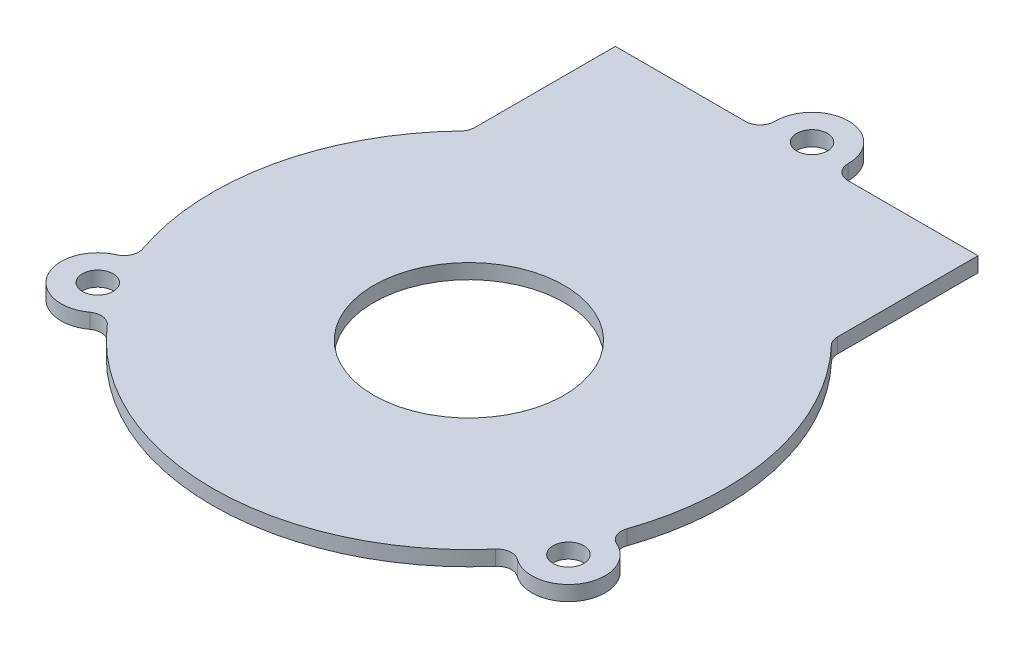
SolidWorks part; units mm, degrees
ref_plane "Front Plane" through (0, 0, 0) normal (0, 0, 1) x (1, 0, 0)
ref_plane "Top Plane" through (0, 0, 0) normal (0, 1, 0) x (1, 0, 0)
ref_plane "Right Plane" through (0, 0, 0) normal (1, 0, 0) x (0, 0, -1)
sketch "Sketch13" plane through (0, 0, 0) normal (0, 1, 0) x (1, 0, 0)
  circle A0 centre (0, 0) radius 35
extrude "Boss-Extrude3" add sketch "Sketch13" along normal blind 2.032
sketch "Sketch14" plane through (0, 2.032, 0) normal (0, 1, 0) x (1, 0, 0)
  line L0 (-24.7478, 24.7497) -> (24.7477, 24.7498)
  line L1 (-24.7478, 24.7497) -> (-24.7479, 44.7452)
  line L2 (24.7477, 24.7498) -> (24.7476, 44.7454)
  line L3 (-24.7479, 44.7452) -> (24.7476, 44.7454)
  line L4 (0, 0) -> (60.4611, -34.8658) construction
  line L5 (0, 0) -> (-56.6044, -32.6614) construction
  line L7 (-3.939, 44.1714) -> (-8.8985, 44.1714)
  line L8 (-3.939, 44.1714) -> (-3.939, 47.547)
  line L9 (-3.939, 47.547) -> (-8.8985, 47.547)
  line L10 (-8.8985, 44.1714) -> (-8.8985, 47.547)
  arc A0 (0, 35) -> (-24.7478, 24.7497) centre (0, 0) ccw construction
  circle A1 centre (0, 0) radius 35 construction
  arc A2 (0, 35) -> (-30.3109, -17.4999) centre (0, 0) ccw construction
  arc A3 (0, 35) -> (30.3118, -17.4984) centre (0, 0) ccw
  arc A4 (0, 35) -> (24.7477, 24.7498) centre (0, 0) ccw construction
  circle A5 centre (32.1365, -18.5413) radius 2.1017
  circle A6 centre (32.1365, -18.5413) radius 4.9951
  circle A7 centre (-32.1465, -18.5162) radius 2.0981
  circle A8 centre (-32.1465, -18.5162) radius 4.9995
extrude "Boss-Extrude4" add sketch "Sketch14" against normal up to surface (2.032 mm away) contours L0 L1 L3 L2 up to face at (0, 0, 35)
sketch "Sketch15" plane through (0, 2.032, 0) normal (0, 1, 0) x (1, 0, 0)
  line L0 (0, 0) -> (0, 62.3966) construction
  line L1 (-0.0001, 44.7453) -> (0, 46.8414) construction
  line L2 (-24.7479, 44.7452) -> (24.7476, 44.7454) construction
  circle A0 centre (0, 46.8414) radius 2.0961
  circle A1 centre (0, 46.8414) radius 4.996
extrude "Boss-Extrude11" add sketch "Sketch15" against normal up to surface (2.032 mm away) contours A1 | A0 up to face at (-0.0001, 0, -19.8101)
extrude "Boss-Extrude12" add sketch "Sketch14<6>" against normal up to surface (2.032 mm away) contours A6 up to face at (0, 0, -29.3038)
sketch "Sketch14<6>" plane through (0, 2.032, 0) normal (0, 1, 0) x (1, 0, 0) same geometry as "Sketch14"
extrude "Boss-Extrude14" add sketch "Sketch14<8>" against normal up to surface (2.032 mm away) contours L0 A5 region at (32.1365, 2.032, 18.5413) up to face at (5.9749, 0, -21.2696)
sketch "Sketch14<8>" plane through (0, 2.032, 0) normal (0, 1, 0) x (1, 0, 0) same geometry as "Sketch14"
hole_wizard "Ø4.2 (4.2) Diameter Hole1" positions "Sketch22" profile "Sketch23" hole size "Ø4.2" standard "ANSI Metric" end condition through all
sketch "Sketch22" plane through (0, 2.032, 0) normal (0, 1, 0) x (1, 0, 0)
  point P0 (32.1248, -18.5356)
sketch "Sketch23" plane through (32.1248, 2.032, 18.5356) normal (1, 0, 0) x (0, 0, 1)
  line L0 (0, 0) -> (0, 2.032)
  line L1 (0, 2.032) -> (2.1, 2.032)
  line L2 (2.1, 2.032) -> (2.1, 0)
  line L5 (2.1, 0) -> (0, 0)
  line L11 (0, -6.35) -> (0, 107.95) construction
  dimension "Thru Hole Dia." = 4.2
  dimension "Thru Hole Depth" = 2.032
extrude "Boss-Extrude15" add sketch "Sketch14<11>" against normal up to surface (2.032 mm away) contours A8 up to face at (32.1248, 0, 20.6356)
sketch "Sketch14<11>" plane through (0, 2.032, 0) normal (0, 1, 0) x (1, 0, 0) same geometry as "Sketch14"
hole_wizard "Ø4.2 (4.2) Diameter Hole2" positions "Sketch26" profile "Sketch27" hole size "Ø4.2" standard "ANSI Metric" end condition through all
sketch "Sketch26" plane through (0, 2.032, 0) normal (0, 1, 0) x (1, 0, 0)
  point P0 (-32.148, -18.5088)
  point P2 (-32.148, -18.5088)
sketch "Sketch27" plane through (-32.148, 2.032, 18.5088) normal (1, 0, 0) x (0, 0, 1)
  line L0 (0, 0) -> (0, 2.032)
  line L1 (0, 2.032) -> (2.1, 2.032)
  line L2 (2.1, 2.032) -> (2.1, 0)
  line L5 (2.1, 0) -> (0, 0)
  line L11 (0, -6.35) -> (0, 107.95) construction
  dimension "Thru Hole Dia." = 4.2
  dimension "Thru Hole Depth" = 2.032
fillet "Fillet4" radius 2 1 edges at (-24.7478, 1.016, -24.7497)
fillet "Fillet6" radius 2 1 edges at (-32.2839, 1.016, 13.5185)
fillet "Fillet7" radius 2 1 edges at (-27.8924, 1.016, 21.1427)
fillet "Fillet8" radius 2 1 edges at (27.8812, 1.016, 21.1574)
fillet "Fillet9" radius 2 1 edges at (32.2715, 1.016, 13.548)
fillet "Fillet10" radius 2 1 edges at (24.7477, 1.016, -24.7498)
fillet "Fillet11" radius 2 1 edges at (4.535, 1.016, -44.7453)
fillet "Fillet12" radius 2 1 edges at (-4.535, 1.016, -44.7453)
sketch "Sketch28" plane through (0, 2.032, 0) normal (0, 1, 0) x (1, 0, 0)
  circle A0 centre (0, 0) radius 5
extrude "Cut-Extrude1" cut sketch "Sketch28" against normal up to surface (2.032 mm away) up to face at (-32.148, 0, 20.6088)
sketch "Sketch29" plane through (0, 2.032, 0) normal (0, 1, 0) x (1, 0, 0)
  circle A0 centre (0, 0) radius 13
extrude "Cut-Extrude2" cut sketch "Sketch29" against normal up to surface (2.032 mm away) up to face at (0, 0, 5)
